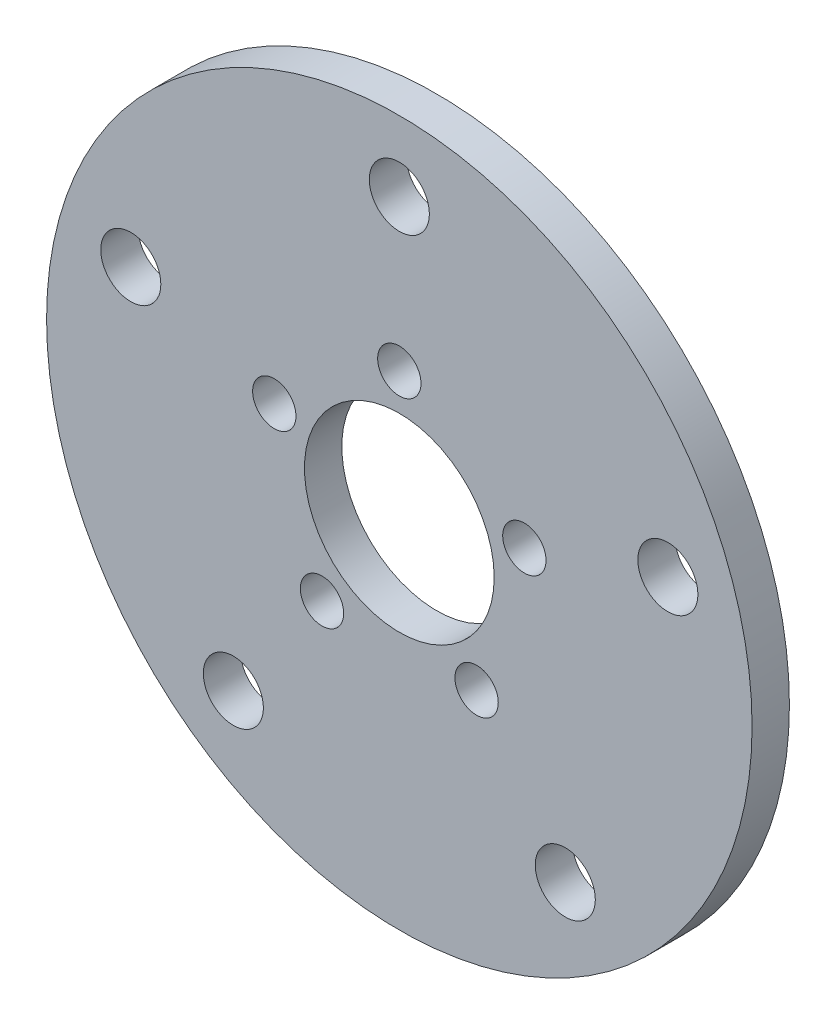
SolidWorks part; units mm, degrees
ref_plane "Front Plane" through (0, 0, 0) normal (0, 0, 1) x (1, 0, 0)
ref_plane "Top Plane" through (0, 0, 0) normal (0, 1, 0) x (1, 0, 0)
ref_plane "Right Plane" through (0, 0, 0) normal (1, 0, 0) x (0, 0, -1)
sketch "Sketch1" plane through (0, 0, 0) normal (0, 0, 1) x (1, 0, 0)
  line L0 (0, 0) -> (0, 11.176) construction
  line L1 (0, 24) -> (0, 0) construction
  circle A0 centre (0, 0) radius 29.9847
  circle A1 centre (0, 0) radius 8.0645
  circle A2 centre (0, 11.176) radius 1.8415
  circle A3 centre (0, 24) radius 2.5527
  circle A4 centre (10.629, 3.4536) radius 1.8415
  circle A5 centre (22.8254, 7.4164) radius 2.5527
  circle A6 centre (6.5691, -9.0416) radius 1.8415
  circle A7 centre (14.1068, -19.4164) radius 2.5527
  circle A8 centre (-6.5691, -9.0416) radius 1.8415
  circle A9 centre (-14.1068, -19.4164) radius 2.5527
  circle A10 centre (-10.629, 3.4536) radius 1.8415
  circle A11 centre (-22.8254, 7.4164) radius 2.5527
  circle A12 centre (0, 0) radius 29.9847 construction
  dimension "D2" = 16.129
  dimension "D4" = 3.683
  dimension "D5" = 5.1054
  dimension "D3" = 11.176
  dimension "D6" = 24
  dimension "D7" = 5
extrude "Boss-Extrude1" add sketch "Sketch1" along normal blind 3.175
